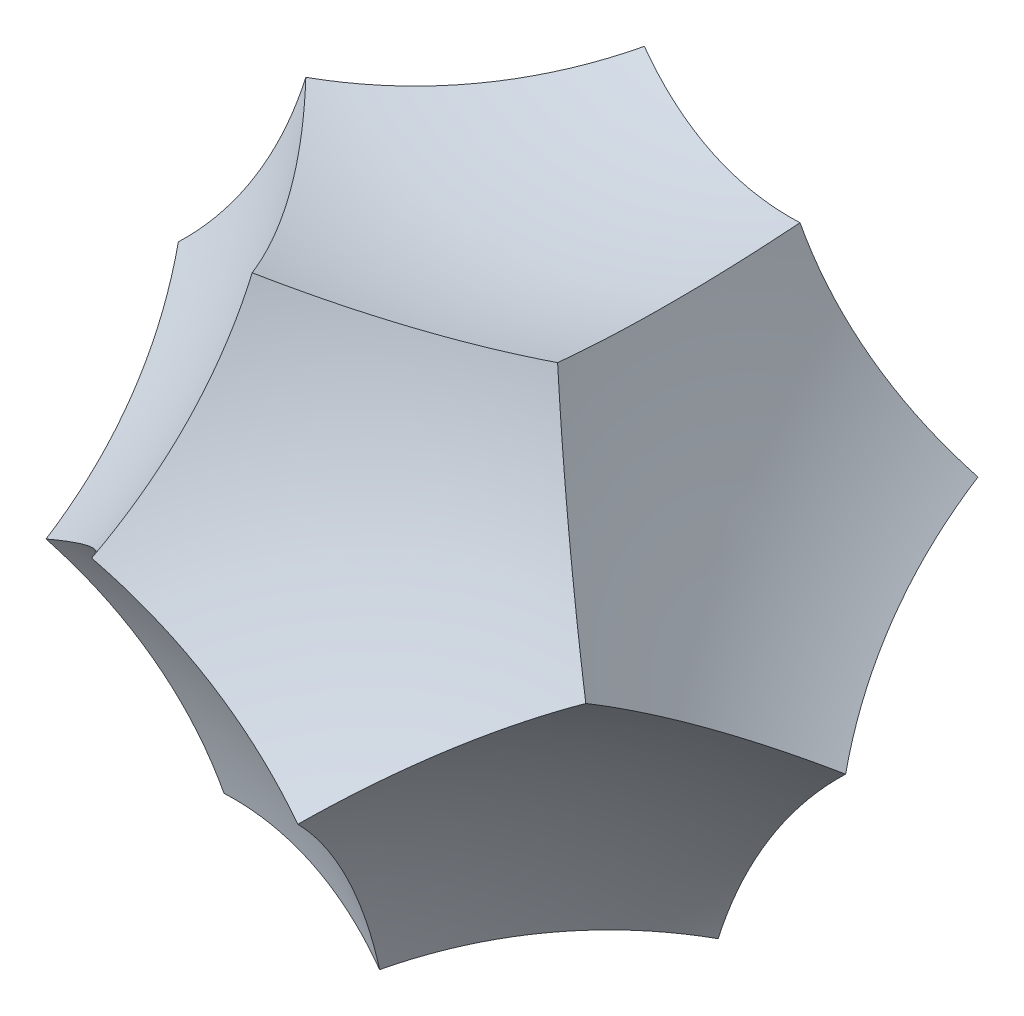
SolidWorks part; units mm, degrees
ref_plane "Front Plane" through (0, 0, 0) normal (0, 0, 1) x (1, 0, 0)
ref_plane "Top Plane" through (0, 0, 0) normal (0, 1, 0) x (1, 0, 0)
ref_plane "Right Plane" through (0, 0, 0) normal (1, 0, 0) x (0, 0, -1)
sketch "Sketch1" plane through (0, 0, 0) normal (0, 1, 0) x (1, 0, 0)
  line L0 (0, -100) -> (0, 100)
  arc A0 (0, 100) -> (0, -100) centre (0, 0) cw
  point P6 (0, 0)
  dimension "D1" = 200
revolve "Revolve1" add sketch "Sketch1" angle 360 about L0
sketch "Sketch2" plane through (0, 0, 0) normal (0, 0, 1) x (1, 0, 0)
  line L0 (0, 245.8432) -> (0, 36.1686)
  arc A0 (0, 245.8432) -> (0, 36.1686) centre (0, 141.0059) ccw
  point P3 (0, 0)
  point P4 (0, 0)
  point P5 (0, 0)
  dimension "D2" = 104.8373
  dimension "D3" = 0
  dimension "D1" = 141.0059
revolve "Cut-Revolve1" cut sketch "Sketch2" angle 360 about L0
mirror "Mirror1" about plane through (0, 0, 0) normal (0, 1, 0) of "Cut-Revolve1"
ref_axis "Axis1" through (0, 0, -110) along (0, 0, 1)
ref_axis "Axis2" through (0, 73.6883, 0) along (0, -1, 0)
pattern_circular "CirPattern1" count 2 every 116.565 about axis through (0, 0, -110) along (0, 0, 1) of "Cut-Revolve1", "Mirror1"
pattern_circular "CirPattern2" count 5 over 360 about axis through (0, 73.6883, 0) along (0, -1, 0) of "CirPattern1"
